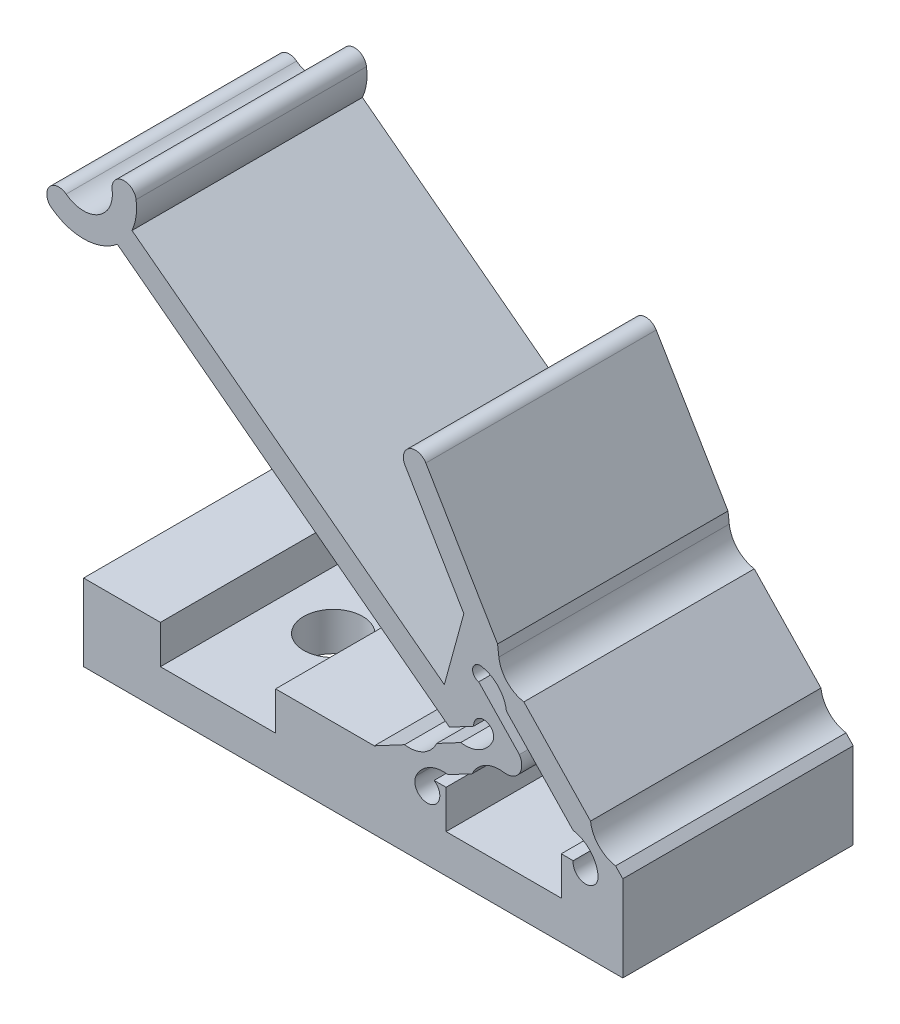
SolidWorks part; units mm, degrees
ref_plane "Front Plane" through (0, 0, 0) normal (0, 0, 1) x (1, 0, 0)
ref_plane "Top Plane" through (0, 0, 0) normal (0, 1, 0) x (1, 0, 0)
ref_plane "Right Plane" through (0, 0, 0) normal (1, 0, 0) x (0, 0, -1)
sketch "Sketch-SkeletonConfig1" plane through (0, 0, 0) normal (0, 0, 1) x (1, 0, 0)
  line L0 (0, 0) -> (0, -50000) construction
  line L1 (0, 0) -> (7.455, 0.2734) construction
  line L2 (9.9233, 0.3639) -> (10.6101, 4.558) construction
  line L3 (10.6101, 4.558) -> (7.9471, 2.8569) construction
  line L4 (7.9471, 2.8569) -> (7.455, 0.2734) construction
  line L5 (10.6101, 4.558) -> (12.0093, 11.478) construction
  line L6 (7.9471, 2.8569) -> (4.1146, 23.199) construction
  line L7 (7.455, 0.2734) -> (9.9233, 0.3639) construction
  line L8 (9.9233, 0.3639) -> (14.65, 0.5372) construction
  line L9 (10.6101, 4.558) -> (13.9821, 6.712) construction
  line L11 (7.9471, 2.8569) -> (5.8206, 1.4986) construction
  dimension "D1" = 92.1
  dimension "D2" = 7.46
  dimension "D3" = 2.47
  dimension "D4" = 4.25
  dimension "D5" = 78.6
  dimension "D6" = 3.16
  dimension "D7" = 7.06
  dimension "D8" = 20.7
  dimension "D10" = 46
  dimension "D11" = 111.9
  dimension "D9" = 2.63
sketch "Sketch-Config1" plane through (0, 0, 0) normal (0, 0, 1) x (1, 0, 0)
  line L0 (8.3979, 2.5516) -> (8.0635, 0.796)
  line L1 (7.4382, 2.8574) -> (6.8464, -0.2493)
  line L2 (8.0635, 0.796) -> (9.496, 0.8485)
  line L3 (10.3506, -0.1208) -> (6.8464, -0.2493) construction
  line L4 (7.9471, 2.8569) -> (7.455, 0.2734) construction
  line L5 (11.5192, 11.5771) -> (10.1621, 4.8651)
  line L6 (7.455, 0.2734) -> (9.9233, 0.3639) construction
  line L7 (10.3506, -0.1208) -> (15.5786, 0.0709) construction
  line L8 (9.9358, 3.5339) -> (8.3979, 2.5516)
  line L9 (10.6101, 4.558) -> (7.9471, 2.8569) construction
  line L10 (9.0969, 0.8339) -> (9.1335, -0.1654) construction
  line L11 (7.2099, 1.6587) -> (8.1922, 1.4716) construction
  line L12 (8.9779, 4.1086) -> (9.5162, 3.2659) construction
  line L15 (9.9233, 0.3639) -> (10.6101, 4.558) construction
  line L16 (9.8006, 2.7086) -> (10.7875, 2.547) construction
  line L17 (12.4994, 11.3789) -> (11.1519, 4.7144)
  line L18 (10.6101, 4.558) -> (12.0093, 11.478) construction
  line L19 (10.5977, 7.0192) -> (11.5778, 6.821) construction
  line L20 (4.0182, 21.0106) -> (7.4382, 2.8574)
  line L21 (8.3015, 3.6766) -> (5.0009, 21.1957)
  line L22 (7.9471, 2.8569) -> (4.1146, 23.199) construction
  line L23 (6.0985, 9.9681) -> (7.0813, 10.1533) construction
  line L24 (8.3015, 3.6766) -> (10.1621, 4.8651)
  line L25 (10.5155, 0.8859) -> (13.3219, 0.9888)
  line L26 (10.6101, 4.558) -> (14.4503, 0.5299) construction
  line L27 (-199855.7554, -7328.3779) -> (199880.3288, 7329.2789) construction
  line L28 (11.1519, 4.7144) -> (15.5786, 0.0709)
  line L29 (13.3219, 0.9888) -> (10.9575, 3.469)
  line L30 (12.6946, 1.6469) -> (13.4184, 2.3369) construction
  line L32 (9.496, 0.8485) -> (10.5155, 0.8859)
  line L33 (9.9358, 3.5339) -> (10.5323, 3.915)
  line L34 (6.8464, -0.2493) -> (6.8464, -2.379)
  line L35 (10.9575, 3.469) -> (10.5323, 3.915)
  line L36 (6.8464, -2.379) -> (15.5786, -2.379)
  line L37 (15.5786, -2.379) -> (15.5786, 0.0709)
  line L38 (1.9619, 22.7935) -> (6.2674, 23.6046) construction
  arc A0 (11.5192, 11.5771) -> (12.4994, 11.3789) centre (12.0093, 11.478) cw
  arc A2 (2.9446, 22.9786) -> (5.2847, 23.4195) centre (4.1146, 23.199) ccw
  arc A3 (5.0009, 21.1957) -> (6.2674, 23.6046) centre (4.1146, 23.199) ccw
  arc A4 (1.9619, 22.7935) -> (2.9446, 22.9786) centre (2.4533, 22.886) cw
  arc A5 (6.2674, 23.6046) -> (5.2847, 23.4195) centre (5.776, 23.512) ccw
  arc A6 (1.9619, 22.7935) -> (4.0182, 21.0106) centre (4.1146, 23.199) ccw
  point P25 (9.247, 3.6873)
  point P27 (7.701, 1.5651)
  point P28 (9.1152, 0.3342)
  point P36 (10.2941, 2.6278)
  point P38 (11.0877, 6.9201)
  point P51 (6.5899, 10.0607)
  point P61 (13.0565, 1.9919)
  dimension "D3" = 2.3812
  dimension "D4" = 4.3812
  dimension "D1" = 1
  dimension "D2" = 3.175
  dimension "D5" = 7
extrude "Boss-Config1" [suppressed] add sketch "Sketch-Config1" along normal blind 6.35
sketch "Sketch-SkeletonConfig2" plane through (0, 0, 0) normal (0, 0, 1) x (1, 0, 0)
  line L0 (0, 0) -> (0, -50000) construction
  line L1 (0, 0) -> (7.455, 0.2734) construction
  line L2 (9.9233, 0.3639) -> (10.6101, 4.558) construction
  line L3 (10.6101, 4.558) -> (9.7761, 1.5101) construction
  line L4 (9.7761, 1.5101) -> (7.455, 0.2734) construction
  line L5 (10.6101, 4.558) -> (7.0062, 10.6288) construction
  line L6 (9.7761, 1.5101) -> (-6.7111, 14.0265) construction
  line L7 (7.455, 0.2734) -> (9.9233, 0.3639) construction
  line L8 (5.5834, 0.2047) -> (10.3101, 0.3781) construction
  line L9 (10.6101, 4.558) -> (11.5958, 8.1597) construction
  line L11 (9.7761, 1.5101) -> (8.6058, -2.7665) construction
  dimension "D1" = 92.1
  dimension "D2" = 7.46
  dimension "D3" = 2.47
  dimension "D4" = 4.25
  dimension "D5" = 78.6
  dimension "D6" = 3.16
  dimension "D7" = 7.06
  dimension "D8" = 20.7
  dimension "D10" = 46
  dimension "D11" = 111.9
  dimension "D9" = 2.63
sketch "Sketch-Config2" plane through (0, 0, 0) normal (0, 0, 1) x (1, 0, 0)
  line L3 (7.2122, -0.2359) -> (5.3047, -0.3058) construction
  line L4 (9.7761, 1.5101) -> (-6.7111, 14.0265) construction
  line L6 (-199860.0954, -7328.537) -> (199875.9888, 7329.1198) construction
  line L7 (9.8853, -0.1379) -> (15.5786, 0.0709) construction
  line L9 (7.455, 0.2734) -> (9.9233, 0.3639) construction
  line L10 (10.9008, 0.9001) -> (10.9374, -0.0993) construction
  line L15 (9.3493, 0.7161) -> (8.352, 0.1848)
  line L18 (8.512, 1.4031) -> (8.9823, 0.5206) construction
  line L19 (6.5762, 10.3736) -> (9.0074, 6.2784)
  line L20 (-5.3148, 12.3387) -> (8.4132, 1.917)
  line L21 (8.2015, 3.3332) -> (-4.7101, 13.1352)
  line L22 (9.7761, 1.5101) -> (7.455, 0.2734) construction
  line L23 (2.9291, 6.0802) -> (3.5338, 6.8767) construction
  line L26 (10.6101, 4.558) -> (14.4503, 0.5299) construction
  line L27 (10.0719, 4.4853) -> (9.4891, 2.3557) construction
  line L28 (11.0112, 4.862) -> (15.5786, 0.0709) construction
  line L29 (14.5562, -0.3058) -> (10.7658, 3.6702) construction
  line L30 (12.9938, 1.3331) -> (13.7176, 2.0231) construction
  line L34 (5.3047, -0.3058) -> (5.3047, -3.4808) construction
  line L36 (5.3047, -3.4808) -> (15.5786, -3.4808)
  line L37 (15.5786, -3.4808) -> (15.5786, 0.0709)
  line L38 (-8.0357, 12.2817) -> (-6.0162, 14.9419) construction
  line L39 (10.6101, 4.558) -> (9.7761, 1.5101) construction
  line L40 (9.7791, 3.4154) -> (10.7436, 3.1515) construction
  line L42 (7.4361, 10.8841) -> (10.4021, 5.8879)
  line L43 (8.1032, 7.8014) -> (8.9631, 8.3119) construction
  line L44 (10.6101, 4.558) -> (7.0062, 10.6288) construction
  line L45 (7.7789, -0.3058) -> (5.3047, -0.3058) construction
  line L46 (14.5562, -0.3058) -> (15.5786, -0.3058) construction
  line L47 (13.528, -0.3058) -> (7.7789, -0.3058)
  line L48 (9.0074, 6.2784) -> (8.2015, 3.3332)
  line L49 (15.5786, 0.0709) -> (15.28, 0.3842)
  line L50 (10.7658, 3.6702) -> (9.4891, 5.0093) construction
  line L51 (15.28, 0.3842) -> (14.5562, -0.3058) construction
  line L52 (14.5815, 0.7545) -> (14.7625, 0.927) construction
  line L53 (13.5212, 0.7799) -> (14.2449, 1.4699) construction
  line L54 (11.0112, 4.862) -> (9.8498, 6.0802) construction
  line L55 (10.7911, 4.7305) -> (10.972, 4.903) construction
  line L56 (9.7307, 4.7558) -> (10.4545, 5.4459) construction
  line L57 (10.7658, 3.6702) -> (11.4896, 4.3602) construction
  line L58 (10.7911, 4.7305) -> (10.4292, 4.3855) construction
  line L59 (11.4896, 4.3602) -> (14.2449, 1.4699)
  line L60 (13.5212, 0.7799) -> (10.7658, 3.6702)
  line L61 (10.4545, 5.4459) -> (10.4021, 5.8879)
  line L62 (7.3374, 0.494) -> (7.2199, 0.7146) construction
  line L63 (7.0282, -0.5206) -> (6.3041, -0.9064) construction
  line L64 (7.8818, 1.0673) -> (8.352, 0.1848) construction
  line L65 (6.558, 0.362) -> (7.0282, -0.5206) construction
  line L66 (6.558, 0.362) -> (5.3047, -0.3058)
  line L67 (6.558, 0.362) -> (7.8818, 1.0673) construction
  line L68 (7.3374, 0.494) -> (7.5725, 0.0527) construction
  line L69 (10.2029, 2.304) -> (10.8079, 2.6264) construction
  line L70 (10.6731, 1.4215) -> (11.1125, 1.6556) construction
  line L71 (9.6585, 1.7307) -> (9.541, 1.9513) construction
  line L72 (8.8791, 1.5987) -> (9.3493, 0.7161) construction
  line L73 (10.2029, 2.304) -> (10.6731, 1.4215) construction
  line L74 (9.6585, 1.7307) -> (9.8936, 1.2894) construction
  line L75 (7.8818, 1.0673) -> (8.8791, 1.5987)
  line L76 (8.4132, 1.917) -> (9.4143, 2.4504)
  line L77 (9.6228, 4.1445) -> (11.1323, 2.561)
  line L78 (11.1323, 2.561) -> (11.3028, 2.3822)
  line L79 (-6.7111, 14.0265) -> (-5.0362, 14.2558) construction
  line L80 (-6.7111, 14.0265) -> (-6.7111, -3.4808) construction
  line L81 (5.3047, -3.4808) -> (-6.7111, -3.4808)
  line L82 (-6.7111, -3.4808) -> (-6.7111, -0.3058)
  line L83 (-6.7111, -0.3058) -> (5.3047, -0.3058)
  arc A2 (-7.4311, 13.0782) -> (-5.5316, 14.188) centre (-6.7111, 14.0265) ccw
  arc A3 (-4.7101, 13.1352) -> (-4.5408, 14.3236) centre (-6.7111, 14.0265) ccw
  arc A4 (-8.0357, 12.2817) -> (-7.4311, 13.0782) centre (-7.7334, 12.68) cw
  arc A5 (-4.5408, 14.3236) -> (-5.5316, 14.188) centre (-5.0362, 14.2558) ccw
  arc A6 (-8.0357, 12.2817) -> (-5.3148, 12.3387) centre (-6.7111, 14.0265) ccw
  arc A7 (6.5762, 10.3736) -> (7.4361, 10.8841) centre (7.0062, 10.6288) cw
  arc A8 (15.28, 0.3842) -> (14.2449, 1.4699) centre (15.4863, 1.6171) cw
  arc A9 (14.5562, -0.3058) -> (13.5212, 0.7799) centre (13.3149, -0.453) ccw
  arc A10 (10.4545, 5.4459) -> (11.4896, 4.3602) centre (11.6958, 5.593) ccw
  arc A11 (9.7307, 4.7558) -> (10.7658, 3.6702) centre (9.5245, 3.523) cw
  arc A12 (7.8818, 1.0673) -> (6.558, 0.362) centre (6.7496, 1.5972) cw
  arc A13 (7.0282, -0.5206) -> (8.352, 0.1848) centre (8.1603, -1.0505) cw
  arc A14 (7.0282, -0.5206) -> (7.7789, -0.3058) centre (7.4971, -0.74) ccw
  arc A15 (8.8791, 1.5987) -> (10.2029, 2.304) centre (9.0707, 2.8339) ccw
  arc A16 (9.3493, 0.7161) -> (10.6731, 1.4215) centre (10.4814, 0.1863) cw
  arc A19 (10.2029, 2.304) -> (9.4143, 2.4504) centre (9.8276, 2.4796) ccw
  arc A20 (14.5562, -0.3058) -> (13.528, -0.3058) centre (14.0421, -0.3668) cw
  arc A21 (9.7307, 4.7558) -> (9.6228, 4.1445) centre (9.6795, 4.4497) ccw
  arc A22 (10.6731, 1.4215) -> (11.3028, 2.3822) centre (10.7698, 2.0448) ccw
  point P24 (8.7471, 0.9618)
  point P28 (10.9191, 0.4004)
  point P30 (8.5332, 8.0566)
  point P43 (10.2614, 3.2834)
  point P47 (14.5815, 0.7545)
  point P51 (3.2315, 6.4785)
  point P61 (13.3557, 1.6781)
  dimension "D3" = 2.3812
  dimension "D4" = 4.3812
  dimension "D1" = 1
  dimension "D2" = 3.175
  dimension "D6" = 7
  dimension "D7" = 1.5
  dimension "D9" = 1.5
  dimension "D10" = 0.25
  dimension "D8" = 1.5
  dimension "D11" = 1.5
  dimension "D12" = 1.5
  dimension "D13" = 0.5
  dimension "D14" = 0.5
  dimension "D15" = 45
extrude "Boss-Config2" add sketch "Sketch-Config2" along normal blind 9.525 separate body
sketch "Sketch2" plane through (0.0043, -0.3058, 0) normal (0, -1, 0) x (-1, 0, 0)
  line L0 (6.7155, 0) -> (-15.5743, 0) construction
  line L1 (-13.0304, 0) -> (-8.2679, 0)
  line L2 (-13.0304, 0) -> (-13.0304, -9.525)
  line L3 (-13.0304, -9.525) -> (-8.2679, -9.525)
  line L4 (-8.2679, 0) -> (-8.2679, -9.525)
  line L5 (-13.5237, 0) -> (-13.0304, 0) construction
  line L6 (6.7155, -9.525) -> (6.7155, 0) construction
  line L7 (-8.2679, 0) -> (-7.7746, 0) construction
  line L8 (-7.7746, 0) -> (-13.5237, 0) construction
  line L9 (6.7155, -9.525) -> (-15.5743, -9.525) construction
  line L10 (-15.5743, -4.7625) -> (6.7155, -4.7625) construction
  line L11 (-15.5743, -9.525) -> (-15.5743, 0) construction
  line L12 (-13.0304, 0) -> (-8.2679, -9.525) construction
  line L17 (-13.0304, -9.525) -> (-8.2679, 0) construction
  line L20 (3.5405, -9.525) -> (3.5405, 0)
  line L21 (3.5405, -9.525) -> (-1.222, -9.525)
  line L22 (3.5405, 0) -> (-1.222, 0)
  line L23 (-1.222, -9.525) -> (-1.222, 0)
  line L24 (3.5405, -9.525) -> (-1.222, 0) construction
  line L25 (3.5405, 0) -> (-1.222, -9.525) construction
  point P4 (-10.6492, -4.7625)
  point P12 (-14.5519, 0)
  point P26 (1.1592, -4.7625)
  dimension "D1" = 4.7625
  dimension "D2" = 3.175
extrude "Cut-NutSlot" cut sketch "Sketch2" along normal blind 1.5875
hole_wizard "#2 Clearance Hole1" positions "Sketch4" profile "Sketch3" hole size "#2" standard "ANSI Inch" end condition up to next
sketch "Sketch4" plane through (0, -3.4808, 0) normal (0, -1, 0) x (-1, 0, 0)
  line L16 (-13.0347, 0) -> (-8.2722, -9.525) construction
  point P40 (-10.6535, -4.7625)
  point P44 (1.1549, -4.7625)
sketch "Sketch3" plane through (10.6535, -3.4808, 4.7625) normal (1, 0, 0) x (0, 0, -1)
  line L0 (0, 0) -> (0, 1.5875)
  line L1 (0, 1.5875) -> (1.2192, 1.5875)
  line L2 (1.2192, 1.5875) -> (1.2192, 0)
  line L5 (1.2192, 0) -> (0, 0)
  line L11 (0, -6.35) -> (0, 107.95) construction
  dimension "Thru Hole Dia." = 2.4384
  dimension "Thru Hole Depth" = 1.5875
ref_plane "Plane-Midplane" through (0, 0, 4.7625) normal (0, 0, -1) x (-1, 0, 0)
equation "\"axle-diameter\"=2"
equation "\"switch-thickness\"=12"
equation "\"base-width\"=4.0"
equation "\"axle-bushing-radius\"=3"
equation "\"clearance\"= 0.25"
equation "\"arm-width\"=1.0"
equation "\"min-diameter\"=70"
equation "\"alpha\"=92.1"
equation "\"beta\"=26.0"
equation "\"gamma\"=78.6"
equation "\"delta\"=111.9"
equation "\"epsilon\"=46.0"
equation "\"eta\"=-228.1"
equation "\"l_AB\"=2.47"
equation "\"l_AC\"=2.63"
equation "\"l_BD\"=4.25"
equation "\"l_CD\"=3.16"
equation "\"l_CE\"=20.70"
equation "\"l_DF\"=7.06"
equation "\"l_OA\"=7.46"
equation "\"D1@Sketch-SkeletonConfig1\" = \"alpha\""
equation "\"D2@Sketch-SkeletonConfig1\" = \"l_OA\""
equation "\"D3@Sketch-SkeletonConfig1\" = \"l_AB\""
equation "\"D4@Sketch-SkeletonConfig1\" = \"l_BD\""
equation "\"D5@Sketch-SkeletonConfig1\" = \"gamma\""
equation "\"D6@Sketch-SkeletonConfig1\" = \"l_CD\""
equation "\"D7@Sketch-SkeletonConfig1\" = \"l_DF\""
equation "\"D8@Sketch-SkeletonConfig1\" = \"l_CE\""
equation "\"D10@Sketch-SkeletonConfig1\" = \"epsilon\""
equation "\"D11@Sketch-SkeletonConfig1\" = \"delta\""
equation "\"D9@Sketch-SkeletonConfig1\" = \"l_AC\""
equation "\"D_groove\"=2.3812"
equation "\"D3@Sketch-Config1\" = \"D_groove\""
equation "\"D4@Sketch-Config1\" = \"D_groove\" + 2 * \"arm-width\""
equation "\"D7@Sketch-SkeletonConfig2\"=\"l_DF\""
equation "\"D6@Sketch-SkeletonConfig2\"=\"l_CD\""
equation "\"D2@Sketch-SkeletonConfig2\"=\"l_OA\""
equation "\"D3@Sketch-SkeletonConfig2\"=\"l_AB\""
equation "\"D9@Sketch-SkeletonConfig2\"=\"l_AC\""
equation "\"D8@Sketch-SkeletonConfig2\"=\"l_CE\""
equation "\"D5@Sketch-SkeletonConfig2\"=\"gamma\""
equation "\"D4@Sketch-SkeletonConfig2\"=\"l_BD\""
equation "\"D10@Sketch-SkeletonConfig2\"=\"epsilon\""
equation "\"D11@Sketch-SkeletonConfig2\"=\"delta\""
equation "\"D1@Sketch-SkeletonConfig2\"=\"alpha\""
equation "\"D5@Sketch-Config2\"=\"arm-width\""
equation "\"hinge_length\"=1.5"
equation "\"hinge_depth\"=0.25"
equation "\"D9@Sketch-Config2\"=\"hinge_length\""
equation "\"D10@Sketch-Config2\"=\"hinge_depth\""
equation "\"D8@Sketch-Config2\"=\"hinge_length\""
equation "\"D11@Sketch-Config2\"=\"hinge_length\""
equation "\"D12@Sketch-Config2\"=\"hinge_length\""
